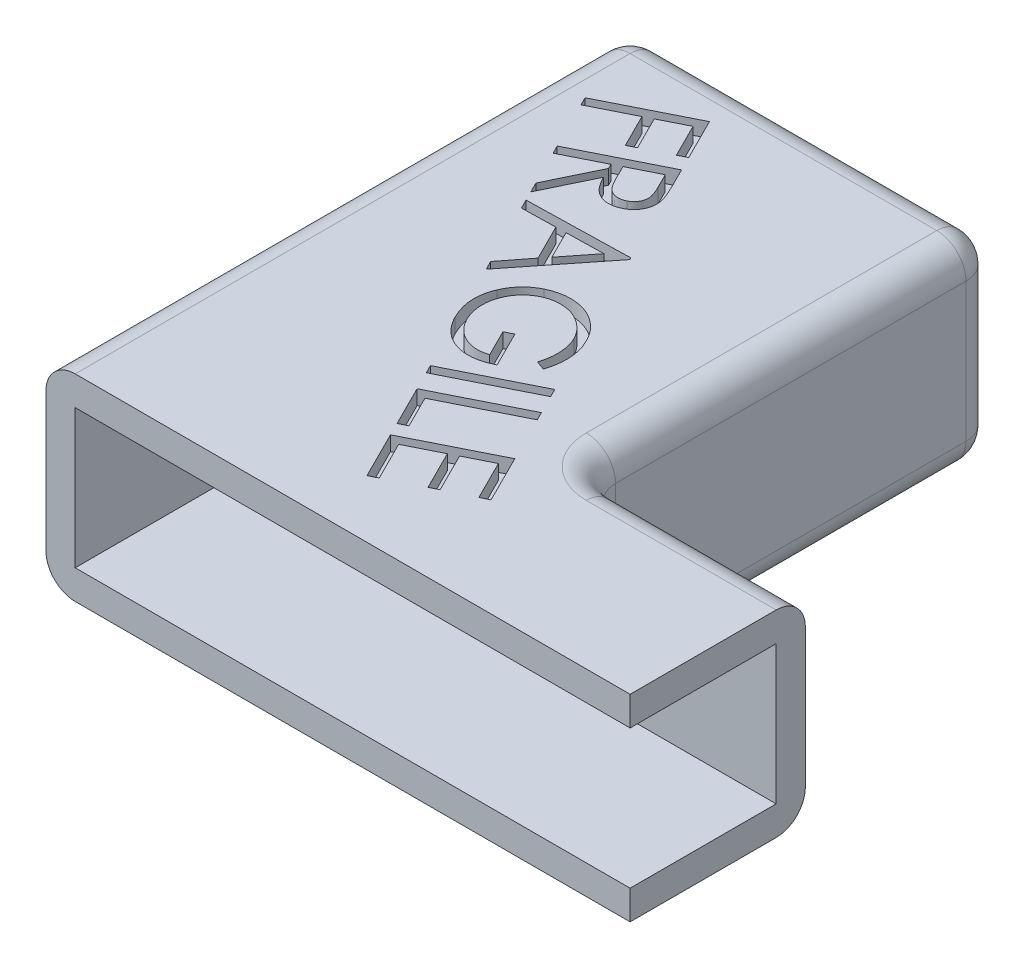
SolidWorks part; units mm, degrees
ref_plane "Front Plane" through (0, 0, 0) normal (0, 0, 1) x (1, 0, 0)
ref_plane "Top Plane" through (0, 0, 0) normal (0, 1, 0) x (1, 0, 0)
ref_plane "Right Plane" through (0, 0, 0) normal (1, 0, 0) x (0, 0, -1)
sketch "Sketch1" plane through (0, 0, 0) normal (0, 1, 0) x (1, 0, 0)
  line L0 (0, 0) -> (0, 40)
  line L5 (0, 40) -> (25, 40)
  line L6 (25, 40) -> (25, 12)
  line L7 (25, 12) -> (40, 12)
  line L8 (40, 12) -> (40, 0)
  line L9 (40, 0) -> (0, 0)
  dimension "D1" = 40
  dimension "D2" = 12
  dimension "D3" = 25
  dimension "D4" = 15
extrude "Boss-Extrude1" add sketch "Sketch1" along normal blind 6.75
sketch "Sketch4" plane through (0, 6.75, 0) normal (0, 1, 0) x (1, 0, 0)
  line L0 (2, 0) -> (2, 38)
  line L1 (0, 0) -> (40, 0) construction
  line L2 (2, 38) -> (23, 38)
  line L3 (23, 38) -> (23, 10)
  line L4 (23, 10) -> (40, 10)
  line L6 (40, 0) -> (2, 0)
  line L7 (0, 40) -> (0, 0) construction
  line L8 (25, 40) -> (0, 40) construction
  line L9 (25, 12) -> (25, 40) construction
  line L10 (40, 12) -> (25, 12) construction
  line L13 (40, 10) -> (40, 0)
  line L14 (40, 0) -> (40, 12) construction
  dimension "D1" = 2
  dimension "D2" = 2
  dimension "D3" = 2
  dimension "D4" = 2
extrude "Cut-Extrude3" cut sketch "Sketch4" against normal blind 4.75
mirror "Mirror2" about plane through (0, 6.75, 0) normal (0, -1, 0) of bodies 104
sketch "Sketch5" plane through (0, 13.5, 0) normal (0, 1, 0) x (1, 0, 0)
  line L0 (0, 40) -> (20, 0) construction
  line L1 (0, 0) -> (40, 0) construction
  line L4 (0, 40) -> (0, 0) construction
  text T0 " FRAGILE" font "Century Gothic" height in points 24
  point P5 (0, 0)
  point P6 (0, 0)
  point P7 (21.9021, 0)
  dimension "D1" = 20
extrude "Cut-Extrude4" cut sketch "Sketch5" against normal blind 1
fillet "Fillet1" radius 2 12 edges at (32.5, 0, -12) (32.5, 13.5, -12) (25, 6.75, -12) (25, 13.5, -26) (25, 0, -26) (12.5, 0, -40) (0, 0, -20) (0, 6.75, -40) (0, 13.5, -20) (12.5, 13.5, -40) (25, 6.75, -40) (23, 6.75, -10)
